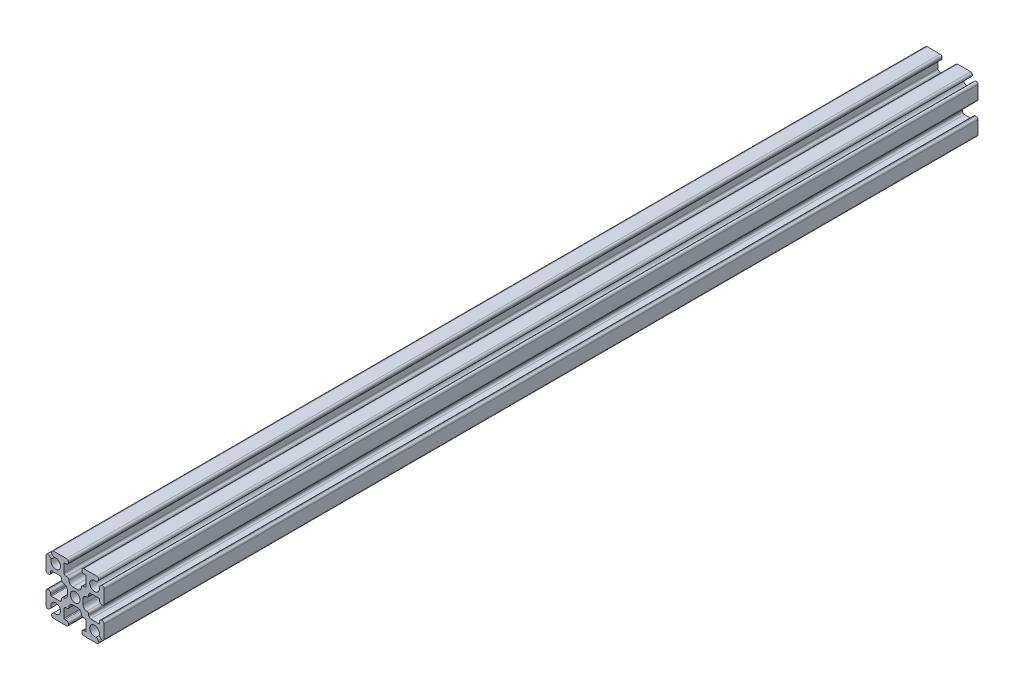
SolidWorks part; units mm, degrees
ref_plane "Front Plane" through (0, 0, 0) normal (0, 0, 1) x (1, 0, 0)
ref_plane "Top Plane" through (0, 0, 0) normal (0, 1, 0) x (1, 0, 0)
ref_plane "Right Plane" through (0, 0, 0) normal (1, 0, 0) x (0, 0, -1)
ref_plane "Plane1" through (0, 0, 0) normal (0, 0, -1) x (-1, 0, 0)
sketch "Sketch1" plane through (0, 0, 0) normal (0, 0, -1) x (-1, 0, 0)
  line L0 (6.6464, 5.9393) -> (6.1636, 5.4565)
  line L1 (5.4565, 6.1636) -> (5.9393, 6.6464)
  line L2 (5.5858, 7.5) -> (2.25, 7.5)
  line L3 (1.75, 7) -> (1.75, 6.8)
  line L4 (2.25, 6.3) -> (2.65, 6.3)
  line L5 (2.85, 6.1) -> (2.85, 4)
  line L6 (2.35, 3.5) -> (2.1, 3.5)
  line L7 (0.6, 2) -> (-0.6, 2)
  line L8 (-2.1, 3.5) -> (-2.35, 3.5)
  line L9 (-2.85, 4) -> (-2.85, 6.1)
  line L10 (-2.65, 6.3) -> (-2.25, 6.3)
  line L11 (-1.75, 6.8) -> (-1.75, 7)
  line L12 (-2.25, 7.5) -> (-5.5858, 7.5)
  line L13 (-5.9393, 6.6464) -> (-5.4565, 6.1636)
  line L14 (-6.1636, 5.4565) -> (-6.6464, 5.9393)
  line L15 (-7.5, 5.5858) -> (-7.5, 2.25)
  line L16 (-7, 1.75) -> (-6.8, 1.75)
  line L17 (-6.3, 2.25) -> (-6.3, 2.65)
  line L18 (-6.1, 2.85) -> (-4, 2.85)
  line L19 (-3.5, 2.35) -> (-3.5, 2.1)
  line L20 (-2, 0.6) -> (-2, -0.6)
  line L21 (-3.5, -2.1) -> (-3.5, -2.35)
  line L22 (-4, -2.85) -> (-6.1, -2.85)
  line L23 (-6.3, -2.65) -> (-6.3, -2.25)
  line L24 (-6.8, -1.75) -> (-7, -1.75)
  line L25 (-7.5, -2.25) -> (-7.5, -5.5858)
  line L26 (-6.6464, -5.9393) -> (-6.1636, -5.4565)
  line L27 (-5.4565, -6.1636) -> (-5.9393, -6.6464)
  line L28 (-5.5858, -7.5) -> (-2.25, -7.5)
  line L29 (-1.75, -7) -> (-1.75, -6.8)
  line L30 (-2.25, -6.3) -> (-2.65, -6.3)
  line L31 (-2.85, -6.1) -> (-2.85, -4)
  line L32 (-2.35, -3.5) -> (-2.1, -3.5)
  line L33 (-0.6, -2) -> (0.6, -2)
  line L34 (2.1, -3.5) -> (2.35, -3.5)
  line L35 (2.85, -4) -> (2.85, -6.1)
  line L36 (2.65, -6.3) -> (2.25, -6.3)
  line L37 (1.75, -6.8) -> (1.75, -7)
  line L38 (2.25, -7.5) -> (5.5858, -7.5)
  line L39 (5.9393, -6.6464) -> (5.4565, -6.1636)
  line L40 (6.1636, -5.4565) -> (6.6464, -5.9393)
  line L41 (7.5, -5.5858) -> (7.5, -2.25)
  line L42 (7, -1.75) -> (6.8, -1.75)
  line L43 (6.3, -2.25) -> (6.3, -2.65)
  line L44 (6.1, -2.85) -> (4, -2.85)
  line L45 (3.5, -2.35) -> (3.5, -2.1)
  line L46 (2, -0.6) -> (2, 0.6)
  line L47 (3.5, 2.1) -> (3.5, 2.35)
  line L48 (4, 2.85) -> (6.1, 2.85)
  line L49 (6.3, 2.65) -> (6.3, 2.25)
  line L50 (6.8, 1.75) -> (7, 1.75)
  line L51 (7.5, 2.25) -> (7.5, 5.5858)
  circle A0 centre (0, 0) radius 1.25
  arc A1 (6.1636, 5.4565) -> (5.4565, 6.1636) centre (5, 5) cw
  arc A2 (5.9393, 6.6464) -> (5.5858, 7.5) centre (5.5858, 7) ccw
  arc A3 (2.25, 7.5) -> (1.75, 7) centre (2.25, 7) ccw
  arc A4 (1.75, 6.8) -> (2.25, 6.3) centre (2.25, 6.8) ccw
  arc A5 (2.65, 6.3) -> (2.85, 6.1) centre (2.65, 6.1) cw
  arc A6 (2.85, 4) -> (2.35, 3.5) centre (2.35, 4) cw
  arc A7 (2.1, 3.5) -> (1.6, 3) centre (2.1, 3) ccw
  arc A8 (1.6, 3) -> (0.6, 2) centre (0.6, 3) cw
  arc A9 (-0.6, 2) -> (-1.6, 3) centre (-0.6, 3) cw
  arc A10 (-1.6, 3) -> (-2.1, 3.5) centre (-2.1, 3) ccw
  arc A11 (-2.35, 3.5) -> (-2.85, 4) centre (-2.35, 4) cw
  arc A12 (-2.85, 6.1) -> (-2.65, 6.3) centre (-2.65, 6.1) cw
  arc A13 (-2.25, 6.3) -> (-1.75, 6.8) centre (-2.25, 6.8) ccw
  arc A14 (-1.75, 7) -> (-2.25, 7.5) centre (-2.25, 7) ccw
  arc A15 (-5.5858, 7.5) -> (-5.9393, 6.6464) centre (-5.5858, 7) ccw
  arc A16 (-5.4565, 6.1636) -> (-6.1636, 5.4565) centre (-5, 5) cw
  arc A17 (-6.6464, 5.9393) -> (-7.5, 5.5858) centre (-7, 5.5858) ccw
  arc A18 (-7.5, 2.25) -> (-7, 1.75) centre (-7, 2.25) ccw
  arc A19 (-6.8, 1.75) -> (-6.3, 2.25) centre (-6.8, 2.25) ccw
  arc A20 (-6.3, 2.65) -> (-6.1, 2.85) centre (-6.1, 2.65) cw
  arc A21 (-4, 2.85) -> (-3.5, 2.35) centre (-4, 2.35) cw
  arc A22 (-3.5, 2.1) -> (-3, 1.6) centre (-3, 2.1) ccw
  arc A23 (-3, 1.6) -> (-2, 0.6) centre (-3, 0.6) cw
  arc A24 (-2, -0.6) -> (-3, -1.6) centre (-3, -0.6) cw
  arc A25 (-3, -1.6) -> (-3.5, -2.1) centre (-3, -2.1) ccw
  arc A26 (-3.5, -2.35) -> (-4, -2.85) centre (-4, -2.35) cw
  arc A27 (-6.1, -2.85) -> (-6.3, -2.65) centre (-6.1, -2.65) cw
  arc A28 (-6.3, -2.25) -> (-6.8, -1.75) centre (-6.8, -2.25) ccw
  arc A29 (-7, -1.75) -> (-7.5, -2.25) centre (-7, -2.25) ccw
  arc A30 (-7.5, -5.5858) -> (-6.6464, -5.9393) centre (-7, -5.5858) ccw
  arc A31 (-6.1636, -5.4565) -> (-5.4565, -6.1636) centre (-5, -5) cw
  arc A32 (-5.9393, -6.6464) -> (-5.5858, -7.5) centre (-5.5858, -7) ccw
  arc A33 (-2.25, -7.5) -> (-1.75, -7) centre (-2.25, -7) ccw
  arc A34 (-1.75, -6.8) -> (-2.25, -6.3) centre (-2.25, -6.8) ccw
  arc A35 (-2.65, -6.3) -> (-2.85, -6.1) centre (-2.65, -6.1) cw
  arc A36 (-2.85, -4) -> (-2.35, -3.5) centre (-2.35, -4) cw
  arc A37 (-2.1, -3.5) -> (-1.6, -3) centre (-2.1, -3) ccw
  arc A38 (-1.6, -3) -> (-0.6, -2) centre (-0.6, -3) cw
  arc A39 (0.6, -2) -> (1.6, -3) centre (0.6, -3) cw
  arc A40 (1.6, -3) -> (2.1, -3.5) centre (2.1, -3) ccw
  arc A41 (2.35, -3.5) -> (2.85, -4) centre (2.35, -4) cw
  arc A42 (2.85, -6.1) -> (2.65, -6.3) centre (2.65, -6.1) cw
  arc A43 (2.25, -6.3) -> (1.75, -6.8) centre (2.25, -6.8) ccw
  arc A44 (1.75, -7) -> (2.25, -7.5) centre (2.25, -7) ccw
  arc A45 (5.5858, -7.5) -> (5.9393, -6.6464) centre (5.5858, -7) ccw
  arc A46 (5.4565, -6.1636) -> (6.1636, -5.4565) centre (5, -5) cw
  arc A47 (6.6464, -5.9393) -> (7.5, -5.5858) centre (7, -5.5858) ccw
  arc A48 (7.5, -2.25) -> (7, -1.75) centre (7, -2.25) ccw
  arc A49 (6.8, -1.75) -> (6.3, -2.25) centre (6.8, -2.25) ccw
  arc A50 (6.3, -2.65) -> (6.1, -2.85) centre (6.1, -2.65) cw
  arc A51 (4, -2.85) -> (3.5, -2.35) centre (4, -2.35) cw
  arc A52 (3.5, -2.1) -> (3, -1.6) centre (3, -2.1) ccw
  arc A53 (3, -1.6) -> (2, -0.6) centre (3, -0.6) cw
  arc A54 (2, 0.6) -> (3, 1.6) centre (3, 0.6) cw
  arc A55 (3, 1.6) -> (3.5, 2.1) centre (3, 2.1) ccw
  arc A56 (3.5, 2.35) -> (4, 2.85) centre (4, 2.35) cw
  arc A57 (6.1, 2.85) -> (6.3, 2.65) centre (6.1, 2.65) cw
  arc A58 (6.3, 2.25) -> (6.8, 1.75) centre (6.8, 2.25) ccw
  arc A59 (7, 1.75) -> (7.5, 2.25) centre (7, 2.25) ccw
  arc A60 (7.5, 5.5858) -> (6.6464, 5.9393) centre (7, 5.5858) ccw
extrude "Boss-Extrude1" add sketch "Sketch1" against normal blind 225
